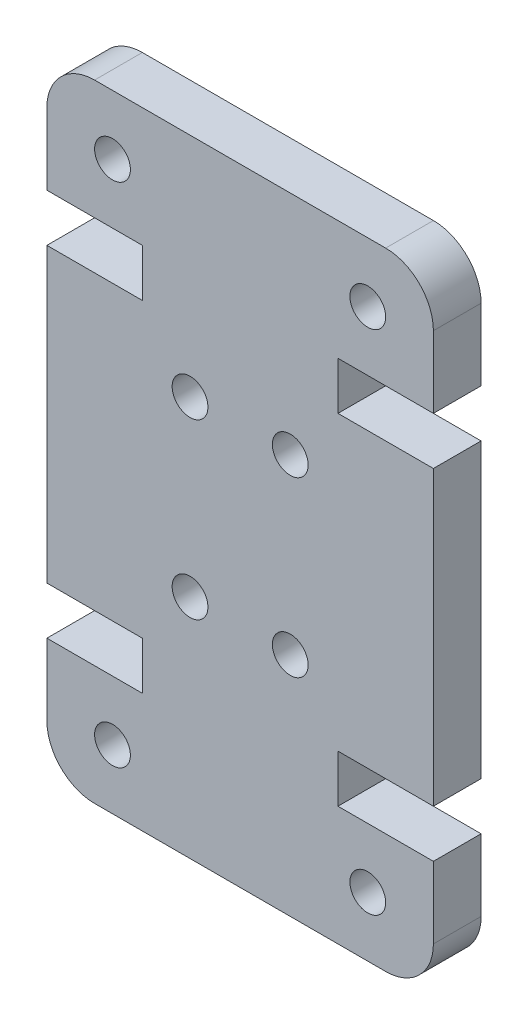
SolidWorks part; units mm, degrees
ref_plane "Front Plane" through (0, 0, 0) normal (0, 0, 1) x (1, 0, 0)
ref_plane "Top Plane" through (0, 0, 0) normal (0, 1, 0) x (1, 0, 0)
ref_plane "Right Plane" through (0, 0, 0) normal (1, 0, 0) x (0, 0, -1)
sketch "Sketch2" plane through (0, 0, 0) normal (0, 0, 1) x (1, 0, 0)
  line L0 (0, 13.13) -> (16.2, 13.13) construction
  line L1 (8.1, 26.26) -> (8.1, 0) construction
  line L2 (0, 7) -> (0, 19.26)
  line L3 (2, 0) -> (14.2, 0)
  line L4 (16.2, 2) -> (16.2, 5)
  line L5 (12.2, 5) -> (16.2, 5)
  line L6 (16.2, 7) -> (12.2, 7)
  line L7 (12.2, 7) -> (12.2, 5)
  line L8 (16.2, 7) -> (16.2, 19.26)
  line L9 (0, 24.26) -> (0, 21.26)
  line L10 (4, 21.26) -> (0, 21.26)
  line L11 (0, 19.26) -> (4, 19.26)
  line L12 (4, 19.26) -> (4, 21.26)
  line L13 (12.2, 19.26) -> (12.2, 21.26)
  line L14 (16.2, 19.26) -> (12.2, 19.26)
  line L15 (12.2, 21.26) -> (16.2, 21.26)
  line L16 (16.2, 24.26) -> (16.2, 21.26)
  line L17 (2, 26.26) -> (14.2, 26.26)
  line L27 (4, 7) -> (4, 5)
  line L30 (0, 7) -> (4, 7)
  line L32 (4, 5) -> (0, 5)
  line L36 (0, 2) -> (0, 5)
  circle A0 centre (13.45, 2.5) radius 0.75
  circle A1 centre (10.2, 9.5) radius 0.75
  arc A2 (16.2, 2) -> (14.2, 0) centre (14.2, 2) cw
  circle A3 centre (2.75, 23.76) radius 0.75
  circle A4 centre (6, 16.76) radius 0.75
  arc A5 (0, 24.26) -> (2, 26.26) centre (2, 24.26) cw
  arc A6 (16.2, 24.26) -> (14.2, 26.26) centre (14.2, 24.26) ccw
  circle A7 centre (10.2, 16.76) radius 0.75
  circle A8 centre (13.45, 23.76) radius 0.75
  arc A17 (0, 2) -> (2, 0) centre (2, 2) ccw
  circle A19 centre (6, 9.5) radius 0.75
  circle A21 centre (2.75, 2.5) radius 0.75
  point P16 (8.1, 13.13)
  dimension "D1" = 1.5
  dimension "D2" = 2
  dimension "D3" = 2.75
  dimension "D4" = 6
  dimension "D5" = 8.1
  dimension "D6" = 2.5
  dimension "D7" = 5
  dimension "D9" = 9.5
  dimension "D10" = 13.13
extrude "Boss-Extrude1" add sketch "Sketch2" along normal blind 4
sketch "Sketch3" plane through (0, 0, 4) normal (0, 0, 1) x (1, 0, 0)
  line L0 (0, 0) -> (0, 26.26)
  line L1 (0, 26.26) -> (16.2, 26.26)
  line L2 (16.2, 26.26) -> (16.2, 0)
  line L3 (16.2, 0) -> (0, 0)
extrude "Cut-Extrude1" cut sketch "Sketch3" against normal blind 2
equation "\"D5@Sketch2\"= \"fingerWidth@parametersSketch@prostheticParameters.SLDPRT\" / 2'Finger Width"
equation "\"D10@Sketch2\"= ( ( \"HL@parametersSketch@prostheticParameters.SLDPRT\" * 0.196 ) - 4 - 6 ) / 2 'PIP Length"
